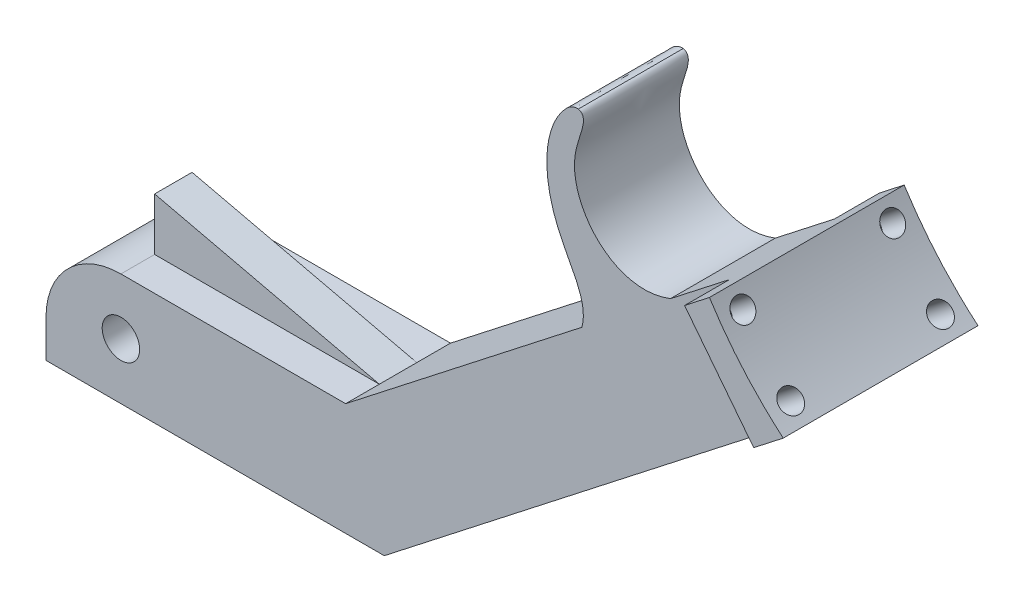
SolidWorks part; units mm, degrees
ref_plane "Alzado" through (0, 0, 0) normal (0, 0, 1) x (1, 0, 0)
ref_plane "Planta" through (0, 0, 0) normal (0, 1, 0) x (1, 0, 0)
ref_plane "Vista lateral" through (0, 0, 0) normal (1, 0, 0) x (0, 0, -1)
sketch "Croquis1" plane through (0, 0, 0) normal (0, 0, 1) x (1, 0, 0)
  line L0 (-73.3375, -31.997) -> (-73.3375, -16.997)
  line L1 (-73.3375, -16.997) -> (-53.3375, -16.997)
  line L2 (-53.3375, -16.997) -> (-33.3375, -16.997)
  line L3 (-33.3375, -16.997) -> (-1.7977, 7.6047)
  line L4 (21.8572, 26.056) -> (31.0828, 14.2285)
  line L5 (31.0828, 14.2285) -> (-28.1791, -31.997)
  line L6 (-28.1791, -31.997) -> (-73.3375, -31.997)
  line L7 (21.8572, 26.056) -> (10.0297, 16.8303)
  spline S0 degree 3 poles (-2.2711, 32.6002) (-3.1207, 32.6509) (-7.1404, 28.9301) (-6.8511, 20.6562) (-2.9703, 13.5979) (-1.1496, 10.0221) (-1.7977, 7.6047) knots 0 0 0 0 0.086866 0.57373 0.743201 1 1 1 1
  spline S1 degree 3 poles (-2.2711, 32.6002) (-1.9579, 32.5713) (-1.551, 32.096) (-1.6256, 30.6782) (-2.2939, 28.9906) (-4.1149, 21.5386) (2.7027, 13.9373) (10.0297, 16.8303) knots 0 0 0 0 0.035853 0.067044 0.168418 0.258673 1 1 1 1
  dimension "D1" = 15
  dimension "D2" = 20
  dimension "D3" = 20
  dimension "D4" = 70
  dimension "D5" = 15
  dimension "D6" = 15
  dimension "D7" = 20
extrude "Saliente-Extruir1" add sketch "Croquis1" along normal mid plane 14
sketch "Croquis2" plane through (0, 0, 7) normal (0, 0, 1) x (1, 0, 0)
  line L0 (-73.3375, -16.997) -> (-73.3375, -31.997) construction
  circle A0 centre (-63.3375, -12.1961) radius 2.5
  dimension "D1" = 5
  dimension "D2" = 10
extrude "Cortar-Extruir1" cut sketch "Croquis2" against normal blind 40 rebuild error yes
sketch "Croquis4" plane through (0, 0, 7) normal (0, 0, 1) x (1, 0, 0)
  line L0 (21.8572, 26.056) -> (17.9147, 22.9807)
  line L1 (31.0828, 14.2285) -> (21.8572, 26.056) construction
  line L2 (21.8572, 26.056) -> (10.0297, 16.8303) construction
  line L3 (17.9147, 22.9807) -> (27.1403, 11.1533)
  line L4 (-28.1791, -31.997) -> (31.0828, 14.2285) construction
  line L5 (27.1403, 11.1533) -> (31.0828, 14.2285)
  line L6 (31.0828, 14.2285) -> (21.8572, 26.056)
  dimension "D1" = 5
extrude "Saliente-Extruir2" add sketch "Croquis4" along normal blind 6
mirror "Simetría1" about plane through (0, 0, 0) normal (0, 0, 1) of "Saliente-Extruir2"
sketch "Croquis5" plane through (0, 0, 13) normal (0, 0, 1) x (1, 0, 0)
  line L0 (21.8572, 26.056) -> (17.9147, 22.9807) construction
  line L1 (21.2279, 25.5651) -> (21.8572, 26.056)
  line L2 (21.8572, 26.056) -> (31.0828, 14.2285)
  spline S0 degree 2 poles (31.0828, 14.2285) (25.2919, 19.1517) (21.2279, 25.5651) knots 0 0 0 1 1 1
extrude "Cortar-Extruir2" cut sketch "Croquis5" against normal through all
sketch "Croquis6" plane through (22.2827, 17.3809, 0) normal (-0.7885, -0.615, 0) x (0, 0, 1)
  line L0 (-13, 7.1019) -> (-7, 7.1019) construction
  line L1 (-13, -7.8981) -> (-7, -7.8981) construction
  circle A0 centre (-20.726, 4.1019) radius 1.5
  circle A1 centre (-20.726, -4.8981) radius 1.5
  dimension "D1" = 3
  dimension "D2" = 3
  dimension "D3" = 3
  dimension "D4" = 3
extrude "Cortar-Extruir3" cut sketch "Croquis6" against normal through all rebuild error yes
mirror "Simetría2" about plane through (0, 0, 0) normal (0, 0, 1) rebuild error yes
sketch "Croquis7" plane through (0, 0, 0) normal (0, 0, 1) x (1, 0, 0)
  line L1 (-33.3375, -16.997) -> (-73.3375, -16.997) construction
  line L3 (-33.3375, -16.997) -> (-47.5676, -16.997)
  line L4 (-47.5676, -16.997) -> (-63.3376, -16.997)
  line L5 (-63.3376, -16.997) -> (-63.3376, -9.997)
  line L6 (-63.3376, -9.997) -> (-33.3375, -16.997)
  dimension "D1" = 15.77
extrude "Saliente-Extruir3" add sketch "Croquis7" along normal mid plane 5
sketch "Croquis8" plane through (22.2827, 17.3809, 0) normal (-0.7885, -0.615, 0) x (0, 0, 1)
  circle A0 centre (-10, 4.4796) radius 1.5
  circle A1 centre (-10, -5.2357) radius 1.5
  dimension "D1" = 3
  dimension "D2" = 3
extrude "Cortar-Extruir4" cut sketch "Croquis8" against normal up to next
mirror "Simetría3" about plane through (0, 0, 0) normal (0, 0, 1) of "Cortar-Extruir4"
sketch "Croquis9" plane through (0, 0, 7) normal (0, 0, 1) x (1, 0, 0)
  line L0 (-73.3375, -16.997) -> (-73.3375, -31.997) construction
  circle A0 centre (-63.3375, -24.497) radius 2.5
  dimension "D1" = 5
  dimension "D2" = 10
extrude "Cortar-Extruir5" cut sketch "Croquis9" against normal up to next
fillet "Redondeo1" radius 10 1 edges at (-73.3375, -16.997, 0)
